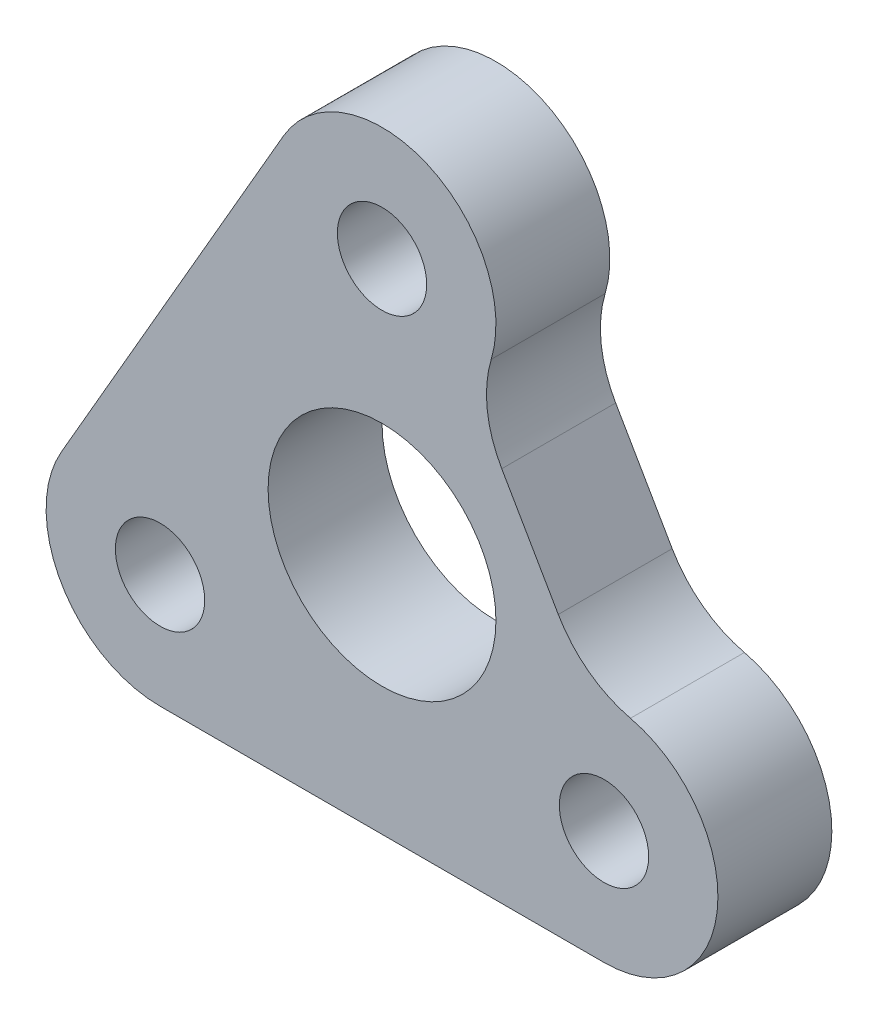
SolidWorks part; units mm, degrees
material "6061-T6 (SS)"
ref_plane "Front Plane" through (0, 0, 0) normal (0, 0, 1) x (1, 0, 0)
ref_plane "Top Plane" through (0, 0, 0) normal (0, 1, 0) x (1, 0, 0)
ref_plane "Right Plane" through (0, 0, 0) normal (1, 0, 0) x (0, 0, -1)
sketch "Sketch1" plane through (0, 0, 0) normal (0, 0, 1) x (1, 0, 0)
  line L3 (0, 14.2875) -> (12.3733, -7.1438) construction
  line L4 (12.3733, -7.1438) -> (-12.3733, -7.1438) construction
  line L5 (-12.3733, -7.1438) -> (0, 14.2875) construction
  line L6 (0, 26.9875) -> (23.3719, -13.4938)
  line L7 (23.3719, -13.4938) -> (-23.3719, -13.4938)
  line L8 (-23.3719, -13.4938) -> (0, 26.9875)
  circle A0 centre (0, 0) radius 6.35
  circle A1 centre (0, 14.2875) radius 2.4892
  circle A2 centre (12.3733, -7.1438) radius 2.4892
  circle A3 centre (-12.3733, -7.1438) radius 2.4892
  point P11 (0, 0)
  dimension "D1" = 12.7
  dimension "D2" = 4.9784
  dimension "D3" = 14.2875
  dimension "D5" = 6.35
  dimension "D4" = 3
extrude "Boss-Extrude1" add sketch "Sketch1" along normal blind 6.35
fillet "Fillet1" radius 6.35 3 edges at (23.3719, -13.4938, 3.175) (-23.3719, -13.4938, 3.175) (0, 26.9875, 3.175)
sketch "Sketch2" plane through (0, 0, 6.35) normal (0, 0, 1) x (1, 0, 0)
  line L0 (5.0055, 10.3802) -> (11.4923, -0.8552)
  line L1 (17.8726, -3.9687) -> (5.4993, 17.4625) construction
  circle A0 centre (0, 14.2875) radius 6.35
  circle A1 centre (12.3733, -7.1438) radius 6.35
  circle A2 centre (0, 0) radius 6.35 construction
  line M4 (17.8726, -3.9687) -> (5.4993, 17.4625)
  dimension "D1" = 12.7
  dimension "D2" = 9.525
extrude "Cut-Extrude1" cut sketch "Sketch2" against normal through all contours A1 A0 L0 M4 region at (10.1242, 5.8452, 6.35)
fillet "Fillet2" radius 6.35 2 edges at (11.4923, -0.8552, 3.175) (5.0055, 10.3802, 3.175)
